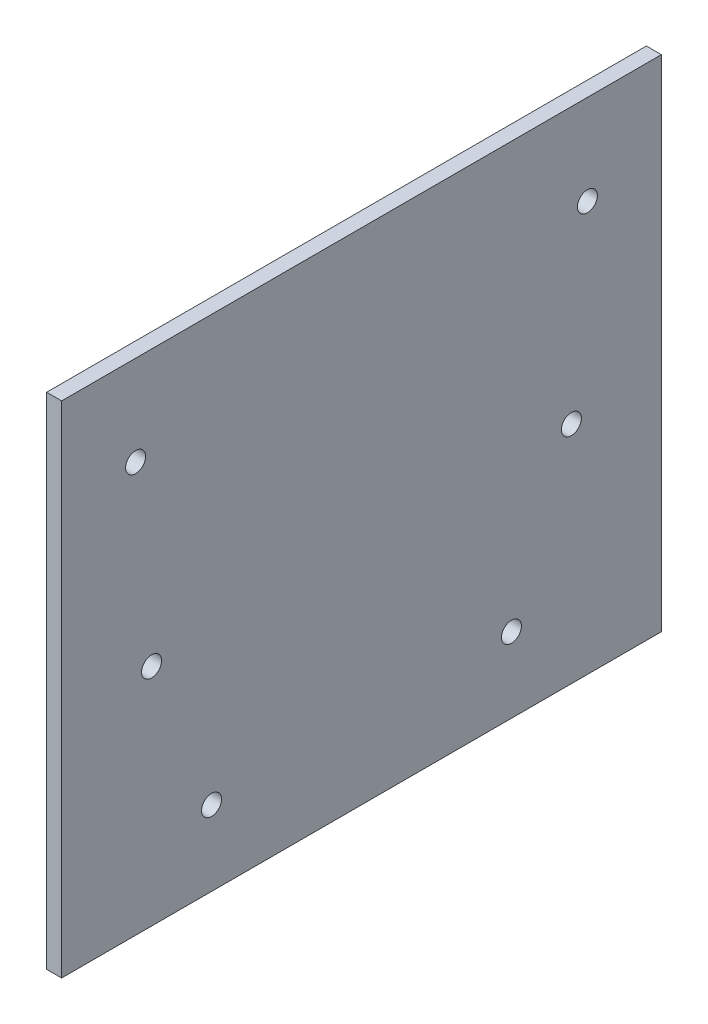
SolidWorks part; units mm, degrees
ref_plane "Front Plane" through (0, 0, 0) normal (0, 0, 1) x (1, 0, 0)
ref_plane "Top Plane" through (0, 0, 0) normal (0, 1, 0) x (1, 0, 0)
ref_plane "Right Plane" through (0, 0, 0) normal (1, 0, 0) x (0, 0, -1)
sketch "Sketch1" plane through (0, 0, 0) normal (1, 0, 0) x (0, 0, -1)
  line L1 (-33.8535, 49.9811) -> (86.1465, 49.9811)
  line L2 (-33.8535, 49.9811) -> (-33.8535, -50.0189)
  line L3 (-33.8535, -50.0189) -> (86.1465, -50.0189)
  line L4 (86.1465, 49.9811) -> (86.1465, -50.0189)
  dimension "D1" = 120
  dimension "D2" = 100
extrude "Boss-Extrude1" add sketch "Sketch1" along normal blind 3
sketch "Sketch2" plane through (3, 0, 0) normal (1, 0, 0) x (0, 0, -1)
  circle A0 centre (-3.8535, -35.0189) radius 2
  circle A1 centre (56.1465, -35.0189) radius 2
  dimension "D1" = 4
  dimension "D2" = 4
extrude "Cut-Extrude1" cut sketch "Sketch2" against normal through all
sketch "Sketch3" plane through (0, 0, 0) normal (-1, 0, 0) x (0, 0, 1)
  circle A0 centre (-68.1465, -5.0189) radius 2
  circle A1 centre (15.8535, -5.0189) radius 2
  dimension "D1" = 4
extrude "Cut-Extrude2" cut sketch "Sketch3" against normal through all
sketch "Sketch4" plane through (0, 0, 0) normal (-1, 0, 0) x (0, 0, 1)
  circle A0 centre (19.0556, 31.9811) radius 2
  circle A1 centre (-71.3485, 31.9811) radius 2
  dimension "D1" = 4
  dimension "D2" = 4
extrude "Cut-Extrude3" cut sketch "Sketch4" against normal through all
